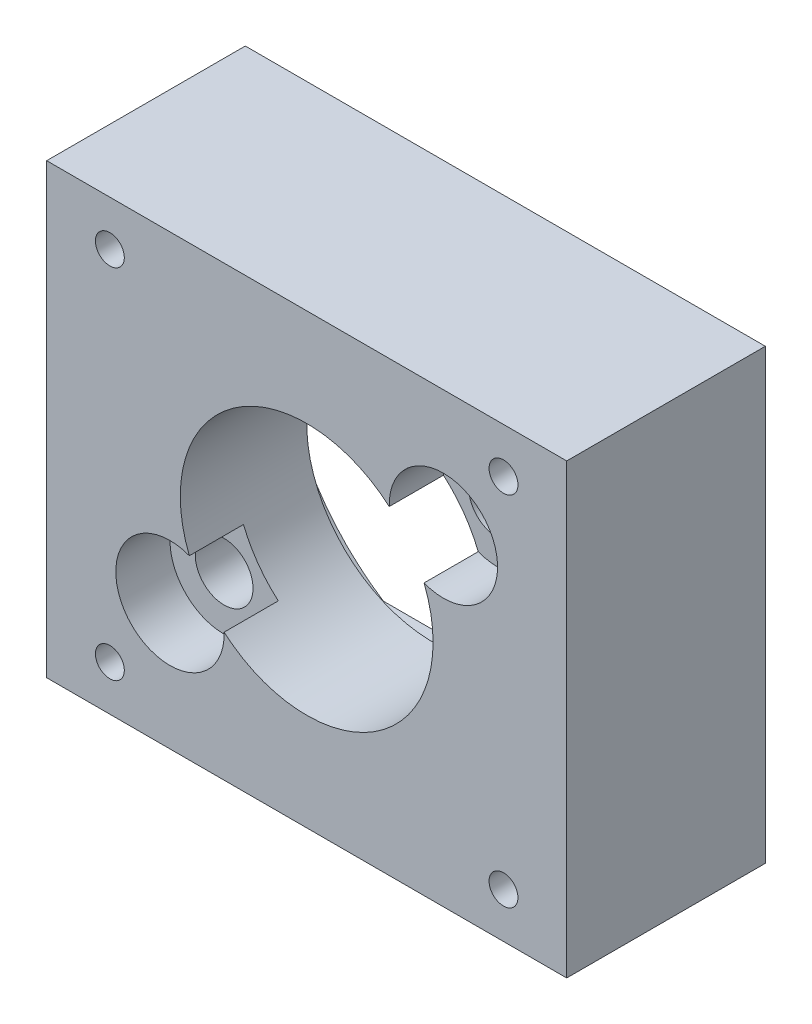
SolidWorks part; units mm, degrees
ref_plane "前视基准面" through (0, 0, 0) normal (0, 0, 1) x (1, 0, 0)
ref_plane "上视基准面" through (0, 0, 0) normal (0, 1, 0) x (1, 0, 0)
ref_plane "右视基准面" through (0, 0, 0) normal (1, 0, 0) x (0, 0, -1)
other "Configuration Table"
sketch "草图1" plane through (0, 0, 0) normal (0, 0, 1) x (1, 0, 0)
  line L5 (-7.2, 6.2) -> (7.2, 6.2)
  line L6 (-7.2, 6.2) -> (-7.2, -6.2)
  line L7 (-7.2, -6.2) -> (7.2, -6.2)
  line L8 (7.2, 6.2) -> (7.2, -6.2)
  line L9 (-7.2, 6.2) -> (7.2, -6.2) construction
  line L10 (-7.2, -6.2) -> (7.2, 6.2) construction
  point P0 (0, 0)
  dimension "D1" = 14.4
  dimension "D2" = 12.4
extrude "凸台-拉伸1" add sketch "草图1" along normal blind 3.5
sketch "草图3" plane through (0, 0, 3.5) normal (0, 0, 1) x (1, 0, 0)
  line L0 (-3.7858, -2.7) -> (3.7858, 2.7) construction
  circle A0 centre (3.7858, 2.7) radius 0.8
  circle A1 centre (-3.7858, -2.7) radius 0.8
  circle A2 centre (3.7858, 2.7) radius 1.5
  circle A3 centre (-3.7858, -2.7) radius 1.5
  circle A4 centre (0, 0) radius 3.5
  dimension "D3" = 3
  dimension "D4" = 1.6
  dimension "D5" = 7
  dimension "D1" = 5.4
  dimension "D2" = 9.3
extrude "切除-拉伸1" cut sketch "草图3" against normal through all contours A0 | A4 | A1
extrude "切除-拉伸2" cut sketch "草图3<3>" against normal offset from surface (1.5 mm away) 2 contours A3 | A2 up to face at (3.5, 0, 0)
sketch "草图3<3>" plane through (0, 0, 3.5) normal (0, 0, 1) x (1, 0, 0) same geometry as "草图3"
sketch "草图4" plane through (0, 0, 0) normal (0, 0, -1) x (-1, 0, 0)
  line L1 (-6.2, 5.2) -> (6.2, 5.2)
  line L2 (-6.2, 5.2) -> (-6.2, -5.2)
  line L3 (-6.2, -5.2) -> (6.2, -5.2)
  line L4 (6.2, 5.2) -> (6.2, -5.2)
  line L5 (-6.2, 5.2) -> (6.2, -5.2) construction
  line L6 (-6.2, -5.2) -> (6.2, 5.2) construction
  circle A0 centre (0, 0) radius 6.2
  point P0 (0, 0)
  line M9 (-7.2, 6.2) -> (-7.2, -6.2)
  line M10 (-7.2, -6.2) -> (7.2, -6.2)
  line M11 (7.2, -6.2) -> (7.2, 6.2)
  line M12 (7.2, 6.2) -> (-7.2, 6.2)
  dimension "D1" = 12.4
  dimension "D2" = 10.4
extrude "凸台-拉伸2" add sketch "草图4" along normal blind 2 contours A0 L3 L2 L1 M12 M9 M10 | A0 L1 L4 L3 M10 M11 M12 | L3 A0 | A0 L2 L3 | A0 L1 L2 | L1 A0 | A0 L4 L1 | A0 L3 L4 region at (6.3434, 2.6, 0) region at (5.4007, 3.9665, 0) region at (0, 5.6029, 0) region at (5.4007, -3.9665, 0) region at (-1.8014, 6.0822, 0) region at (-5.4007, 3.9665, 0) region at (0, -5.6029, 0) region at (-5.4007, -3.9665, 0)
sketch "草图5" plane through (0, 0, 3.5) normal (0, 0, 1) x (1, 0, 0)
  line L0 (7.2, 6.2) -> (-7.2, 6.2) construction
  line L1 (-7.2, 6.2) -> (-7.2, -6.2) construction
  line L2 (-7.2, -6.2) -> (7.2, -6.2) construction
  line L3 (7.2, -6.2) -> (7.2, 6.2) construction
  circle A0 centre (-5.45, 4.95) radius 0.4
  circle A1 centre (5.45, 4.95) radius 0.4
  circle A2 centre (5.45, -4.95) radius 0.4
  circle A3 centre (-5.45, -4.95) radius 0.4
  dimension "D3" = 0.8
  dimension "D1" = 1.25
  dimension "D2" = 1.75
  dimension "D4" = 1.25
  dimension "D5" = 1.75
extrude "切除-拉伸3" cut sketch "草图5" against normal through all
